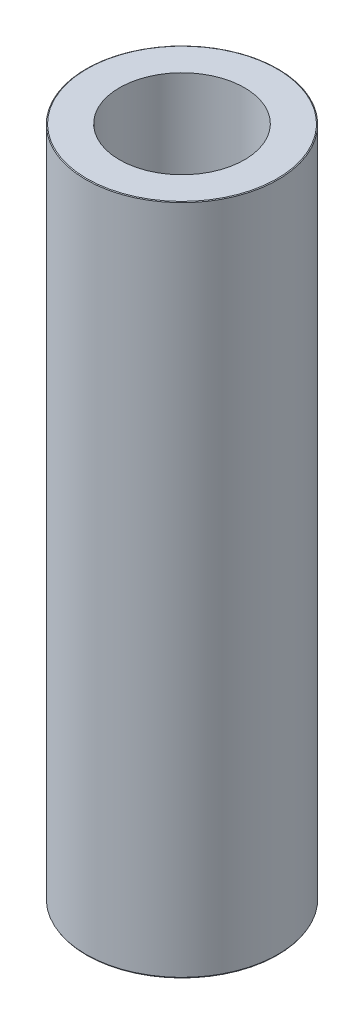
SolidWorks part; units mm, degrees
ref_plane "Front Plane" through (0, 0, 0) normal (0, 0, 1) x (1, 0, 0)
ref_plane "Top Plane" through (0, 0, 0) normal (0, 1, 0) x (1, 0, 0)
ref_plane "Right Plane" through (0, 0, 0) normal (1, 0, 0) x (0, 0, -1)
sketch "Sketch1" plane through (0, 0, 0) normal (0, 1, 0) x (1, 0, 0)
  circle A0 centre (0, 0) radius 60
  dimension "SHAFT_OD" = 120
extrude "Boss-Extrude1" add sketch "Sketch1" along normal blind 420.2779
sketch "Sketch2" plane through (0, 0, 0) normal (0, 1, 0) x (1, 0, 0)
  circle A0 centre (0, 0) radius 39.0718
  dimension "BORE_D" = 78.1437
extrude "Cut-Extrude1" cut sketch "Sketch2" along normal through all
chamfer "Chamfer1" distance 0.3125 angle 60 2 edges at (0, 420.2779, 60) (0, 0, 60) first distance on face at (0, 420.2779, 60) first distance on face at (0, 0, 39.0718)
